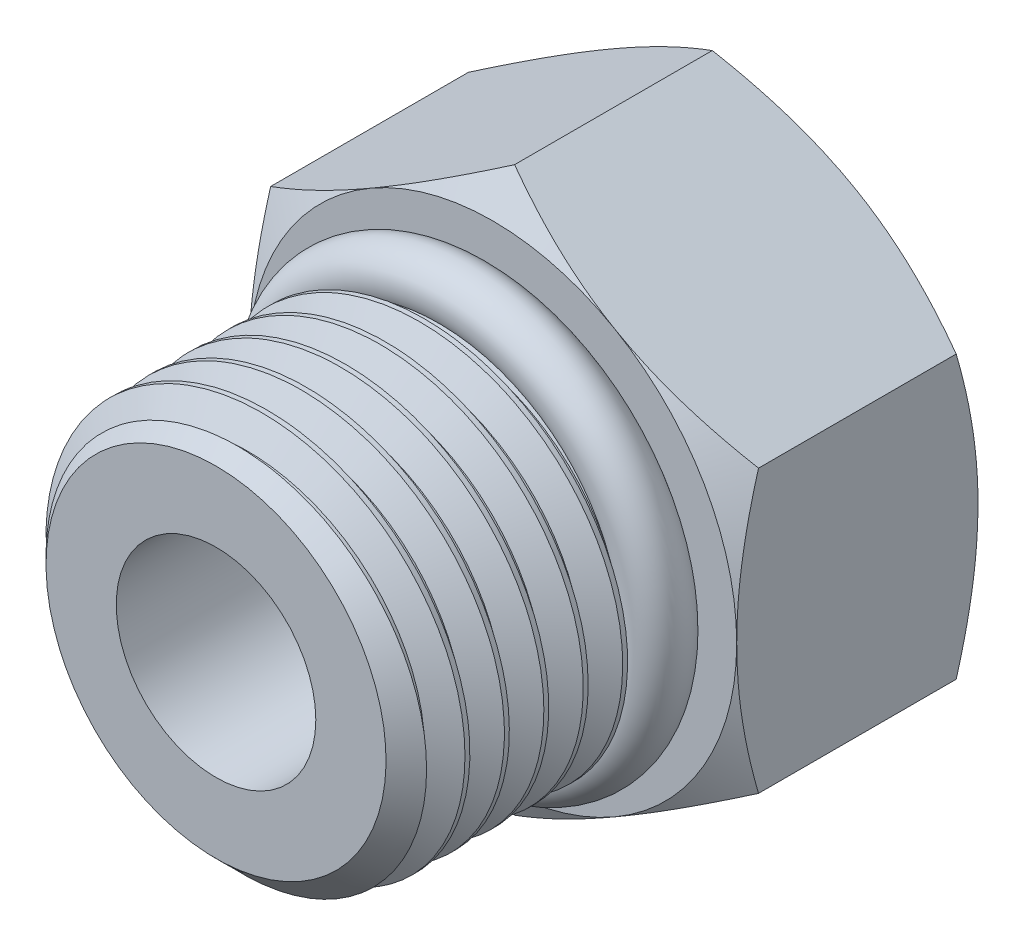
SolidWorks part; units mm, degrees
material "Plain Carbon Steel"
ref_plane "Front Plane" through (0, 0, 0) normal (0, 0, 1) x (1, 0, 0)
ref_plane "Top Plane" through (0, 0, 0) normal (0, 1, 0) x (1, 0, 0)
ref_plane "Right Plane" through (0, 0, 0) normal (1, 0, 0) x (0, 0, -1)
sketch "Sketch1" plane through (0, 0, 0) normal (1, 0, 0) x (0, 0, -1)
  line L0 (-9.271, 0) -> (9.271, 0) construction
  line L1 (-9.271, 7.1437) -> (-9.271, -7.1438) construction
  line L2 (9.271, 8.7312) -> (9.271, -8.7312) construction
  line L3 (-10.5939, 7.2965) -> (-9.1828, 7.2965) construction
  line L4 (-10.5939, 7.2965) -> (-9.8884, 6.0744) construction
  line L5 (-9.8884, 6.0744) -> (-9.1828, 7.2965) construction
  line L6 (-10.5498, 7.2201) -> (-9.2269, 7.2201) construction
  line L7 (-10.5057, 7.1437) -> (-9.271, 7.1437) construction
  line L8 (-9.9766, 6.2272) -> (-9.8002, 6.2272) construction
  line L9 (-9.8884, 6.2272) -> (-9.8884, 6.0744) construction
  line L10 (-9.8884, 7.1437) -> (-9.8884, 7.2965) construction
  line L11 (0.635, 7.1438) -> (0.635, -7.1438) construction
  circle A0 centre (-0.3556, 6.9342) radius 0.9906
  point P3 (-5.7432, -7.1437)
  point P4 (0, 0)
  point P8 (-9.271, 0)
  point P10 (9.271, 0)
  point P23 (-9.8884, 7.2201)
  point P27 (0.635, 0)
  dimension "O-Ring Diameter" = 1.9812
  dimension "Length" = 18.542
  dimension "Thread OD" = 14.2875
  dimension "Drive Size" = 17.4625
  dimension "D1" = 60
  dimension "Thread Pitch" = 1.4111
  dimension "D2" = 0.1764
  dimension "Thread Length" = 9.906
  dimension "D4" = 3.5278
  dimension "O-Ring ID" = 11.8872
sketch "Sketch2" plane through (0, 0, 0) normal (1, 0, 0) x (0, 0, -1)
  line L0 (-9.271, 0) -> (-9.271, 6.0854)
  line L1 (-9.271, 7.1437) -> (-9.271, -7.1438) construction
  line L2 (-9.271, 6.0854) -> (-8.2127, 7.1437)
  line L3 (-8.2127, 7.1437) -> (-1.3462, 7.1437)
  line L4 (0.635, 6.2272) -> (0.635, 0)
  line L6 (0.635, 0) -> (-9.271, 0)
  line L7 (-1.3462, 7.1437) -> (-0.4297, 6.2272)
  line L8 (-0.4297, 6.2272) -> (0.635, 6.2272)
  line L9 (0.635, 7.1438) -> (0.635, -7.1438) construction
  circle A0 centre (-0.3556, 6.9342) radius 0.9906 construction
  circle A1 centre (-0.3556, 6.9342) radius 0.9906 construction
  dimension "D1" = 45
  dimension "D2" = 1.0583
  dimension "D3" = 45
  dimension "D4" = 1.9812
revolve "Revolve1" add sketch "Sketch2" angle 360 about L6
sketch "Sketch3" plane through (0, 0, -0.635) normal (0, 0, -1) x (-1, 0, 0)
  line L1 (0, 10.082) -> (-8.7312, 5.041)
  line L2 (-8.7312, 5.041) -> (-8.7312, -5.041)
  line L3 (-8.7312, -5.041) -> (0, -10.082)
  line L4 (0, -10.082) -> (8.7313, -5.041)
  line L5 (8.7313, -5.041) -> (8.7312, 5.041)
  line L6 (8.7312, 5.041) -> (0, 10.082)
  circle A0 centre (0, 0) radius 8.7312 construction
extrude "Boss-Extrude1" add sketch "Sketch3" along normal up to vertex (8.636 mm away) up to point (0, 0, -9.271)
sketch "Sketch4" plane through (0, 0, -0.635) normal (0, 0, 1) x (1, 0, 0)
  circle A0 centre (0, 0) radius 8.7312 construction
  circle A1 centre (0, 0) radius 8.7312
extrude "Cut-Extrude1" cut sketch "Sketch4" against normal through all draft 60 flip side to cut
sketch "Sketch5" plane through (0, 0, -9.271) normal (0, 0, -1) x (-1, 0, 0)
  circle A0 centre (0, 0) radius 8.7312 construction
  circle A1 centre (0, 0) radius 8.7312
extrude "Cut-Extrude2" cut sketch "Sketch5" against normal through all draft 60 flip side to cut
sketch "Sketch6" plane through (0, 0, 0) normal (1, 0, 0) x (0, 0, -1)
  line L0 (-9.271, 0) -> (-9.271, 3.5719)
  line L1 (-9.271, 7.1437) -> (-9.271, -7.1438) construction
  line L2 (-9.271, 3.5719) -> (2.2225, 3.5719)
  line L3 (2.2225, 3.5719) -> (4.2847, 0)
  line L4 (-9.271, 0) -> (9.271, 0) construction
  line L5 (4.2847, 0) -> (-9.271, 0)
  line L6 (-9.271, 0) -> (9.271, 0) construction
  line L7 (0.635, 7.1438) -> (0.635, -7.1438) construction
  dimension "D1" = 7.1437
  dimension "D2" = 60
  dimension "D3" = 1.5875
revolve "Cut-Revolve1" cut sketch "Sketch6" angle 360 about L6
sketch "Sketch7" plane through (0, 0, 0) normal (1, 0, 0) x (0, 0, -1)
  line L1 (0.635, 7.1438) -> (0.635, -7.1438) construction
  circle A0 centre (-0.3556, 6.9342) radius 0.9906
  circle A1 centre (-0.3556, 6.9342) radius 0.9906 construction
revolve "Revolve2" add sketch "Sketch7" angle 360 about L0
split "Split1" bodies to split 108 resulting bodies 110 111 split by face at (0, 6.2272, -0.635)
sketch "Sketch8" plane through (0, 0, 0) normal (1, 0, 0) x (0, 0, -1)
  line L0 (-10.5498, 7.2201) -> (-9.2269, 7.2201)
  line L1 (-9.2269, 7.2201) -> (-9.8002, 6.2272)
  line L2 (-9.8002, 6.2272) -> (-9.9766, 6.2272)
  line L3 (-9.9766, 6.2272) -> (-10.5498, 7.2201)
sketch "Sketch9" plane through (0, 0, 9.271) normal (0, 0, 1) x (1, 0, 0)
  circle A0 centre (0, 0) radius 7.1437
curve "Helix/Spiral1" pitch 1.4111 height 11.3171 radius 7.1437 centre (0, 0, 9.271) axis (0, 0, -1) start towards (0, 1, 0)
sweep "Cut-Sweep1" cut profiles "Sketch8" path "Helix/Spiral1" align with end faces yes
combine bodies "Combine1" operation type add bodies to combine 112 111
equation "\"D2@Sketch1\"=\"Thread Pitch@Sketch1\"/8"
equation "\"D2@Sketch2\"=\"Thread Pitch@Sketch1\"*.75"
equation "\"D1@Sketch6\"=\"Thread OD@Sketch1\"*.5"
equation "\"D4@Helix/Spiral1\"=\"Thread Pitch@Sketch1\""
equation "\"D3@Helix/Spiral1\"=\"Thread Length@Sketch1\"+\"Thread Pitch@Sketch1\""
equation "\"D4@Sketch1\"=\"Thread Pitch@Sketch1\"*2.5"
equation "\"D4@Sketch2\"=\"O-Ring Diameter@Sketch1\"*1"
